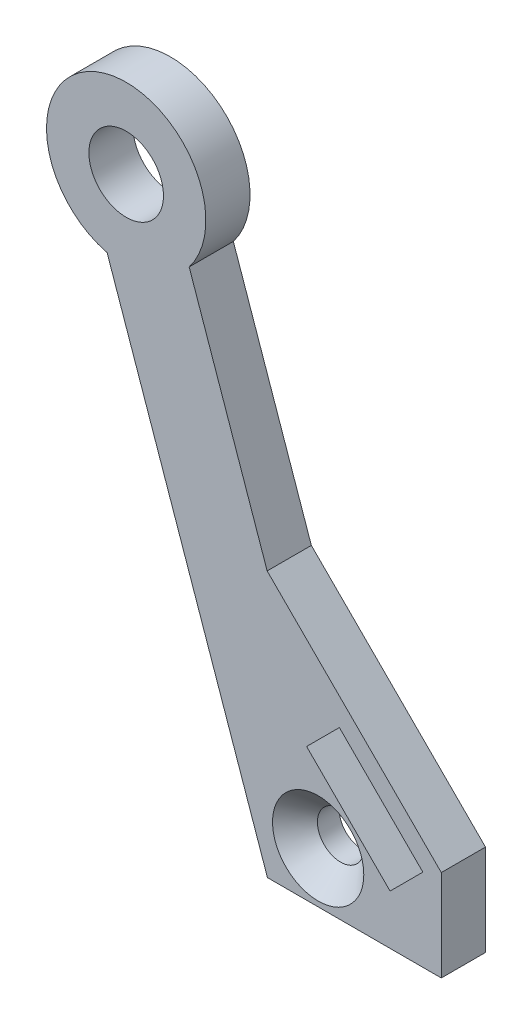
SolidWorks part; units mm, degrees
ref_plane "Front Plane" through (0, 0, 0) normal (0, 0, 1) x (1, 0, 0)
ref_plane "Top Plane" through (0, 0, 0) normal (0, 1, 0) x (1, 0, 0)
ref_plane "Right Plane" through (0, 0, 0) normal (1, 0, 0) x (0, 0, -1)
sketch "Sketch1" plane through (0, 0, 0) normal (0, 0, 1) x (1, 0, 0)
  line L0 (0, 12) -> (12, 0) construction
  line L1 (0, 0) -> (12, 0)
  line L2 (0, 0) -> (0, 12) construction
  line L3 (0, 12) -> (12, 12) construction
  line L4 (12, 0) -> (12, 12) construction
  line L5 (0, 0) -> (3.5, 0)
  line L6 (0, 0) -> (0, 3.5)
  line L7 (0, 3.5) -> (3.5, 3.5) construction
  line L8 (3.5, 0) -> (3.5, 3.5) construction
  line L9 (8.2662, 3.6278) -> (8.3192, 3.6808) construction
  line L10 (8.4645, 3.4295) -> (2.7015, 9.1924)
  line L11 (2.7015, 9.1924) -> (4.9643, 11.4551)
  line L12 (8.4645, 3.4295) -> (10.7272, 5.6922)
  line L13 (4.9643, 11.4551) -> (10.7272, 5.6922)
  line L14 (0, 0) -> (-12.5863, 36.1883)
  line L15 (-12.5863, 36.1883) -> (-6.9193, 38.1593)
  line L16 (-6.9193, 38.1593) -> (-0.0208, 18.3247)
  line L17 (-0.0208, 18.3247) -> (12, 6.3039)
  line L18 (12, 0) -> (8.5175, 3.4825)
  line L19 (12, 6.3039) -> (12, 0)
  line L20 (0, 0) -> (0, 40.9886) construction
  circle A0 centre (3.5, 3.5) radius 1.5
  circle A1 centre (-9.7528, 37.1738) radius 2.575
  circle A3 centre (-9.7528, 37.1738) radius 5.5
  dimension "D5" = 3
  dimension "D6" = 5.15
  dimension "D7" = 11
  dimension "D1" = 12
  dimension "D2" = 12
  dimension "D3" = 3.5
  dimension "D4" = 3.5
  dimension "D8" = 45
  dimension "D9" = 6.3039
  dimension "D10" = 90
  dimension "D11" = 90
  dimension "D12" = 21
  dimension "D13" = 17
  dimension "D14" = 3.2
  dimension "D15" = 8.15
  dimension "D16" = 0.075
  dimension "D17" = 4.925
  dimension "D18" = 6
extrude "Boss-Extrude1" add sketch "Sketch1" along normal blind 3.05 contours L15 A3 A1 | L15 A3 A1 | A3 L14 L2 L10 L11 L13 L3 L17 L16 | L17 L3 L13 L12 L0 L4 | A0 L8 L1 L0 L2 L7 | A0 L7 L2 L1 L8 region at (-0.2787, 14.2067, 0) region at (-13.0484, 41.3827, 0) region at (-8.645, 33.9886, 0)
hole_wizard "CSK for M3 Flat Head Machine Screw1" positions "Sketch2" profile "Sketch3" countersink size "M3" standard "ANSI Metric" end condition through all
sketch "Sketch2" plane through (0, 0, 3.05) normal (0, 0, 1) x (1, 0, 0)
  point P0 (3.5, 3.5)
sketch "Sketch3" plane through (3.5, 3.5, 3.05) normal (1, 0, 0) x (0, -1, 0)
  line L0 (0, 0) -> (0, 3.05)
  line L1 (0, 3.05) -> (1.6, 3.05)
  line L2 (1.6, 3.05) -> (1.6, 1.55)
  line L3 (1.6, 1.55) -> (3.15, 0)
  line L5 (3.15, 0) -> (0, 0)
  line L6 (-1.6, 1.55) -> (-3.15, 0) construction
  line L11 (0, -6.35) -> (0, 107.95) construction
  dimension "Thru Hole Dia." = 3.2
  dimension "Thru Hole Depth" = 3.05
  dimension "Near C'Sink Dia." = 6.3
  dimension "Near C'Sink Angle" = 90
